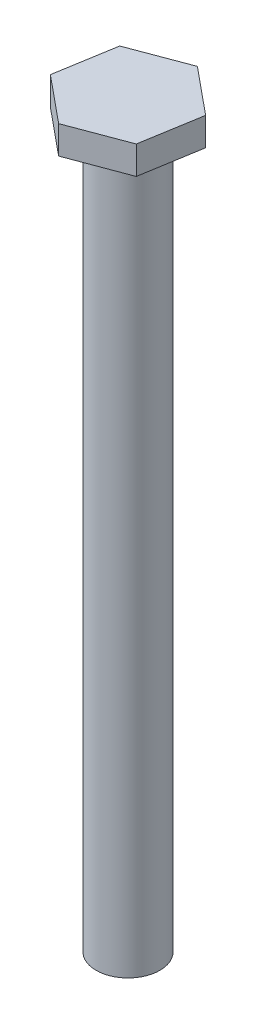
SolidWorks part; units mm, degrees
ref_plane "Front Plane" through (0, 0, 0) normal (0, 0, 1) x (1, 0, 0)
ref_plane "Top Plane" through (0, 0, 0) normal (0, 1, 0) x (1, 0, 0)
ref_plane "Right Plane" through (0, 0, 0) normal (1, 0, 0) x (0, 0, -1)
sketch "Sketch1" plane through (0, 0, 0) normal (0, 1, 0) x (1, 0, 0)
  circle A0 centre (0, 0) radius 7.9375
  dimension "D1" = 15.875
extrude "Shaft" add sketch "Sketch1" against normal blind 177.8
sketch "Sketch2" plane through (0, 0, 0) normal (0, 1, 0) x (1, 0, 0)
  line L1 (11.595, -9.5335) -> (14.0538, 5.2748)
  line L2 (14.0538, 5.2748) -> (2.4588, 14.8084)
  line L3 (2.4588, 14.8084) -> (-11.595, 9.5335)
  line L4 (-11.595, 9.5335) -> (-14.0538, -5.2748)
  line L5 (-14.0538, -5.2748) -> (-2.4588, -14.8084)
  line L6 (-2.4588, -14.8084) -> (11.595, -9.5335)
  circle A0 centre (0, 0) radius 13 construction
  dimension "D1" = 13
extrude "Head" add sketch "Sketch2" along normal blind 7
equation "\"boltLength\" = 7in"
equation "\"boltDiameter\"= 5in / 8"
equation "\"D1@Sketch1\"=\"boltDiameter\""
equation "\"D1@Shaft\" = \"boltLength\""
